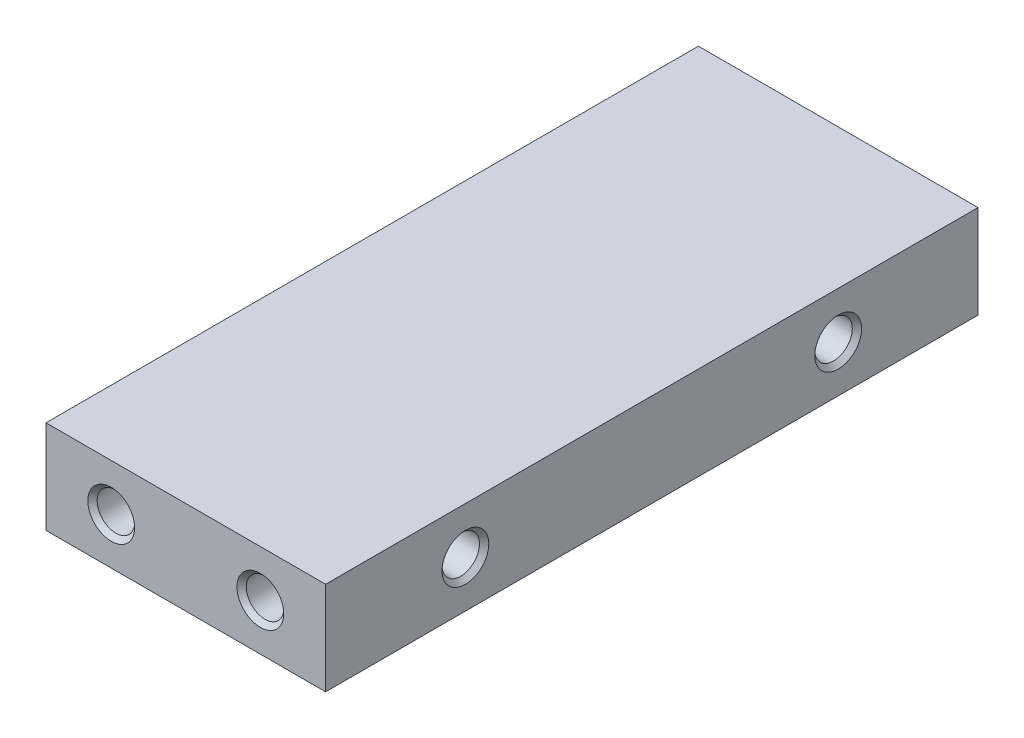
SolidWorks part; units mm, degrees
material "6063-T5"
ref_plane "Front Plane" through (0, 0, 0) normal (0, 0, 1) x (1, 0, 0)
ref_plane "Top Plane" through (0, 0, 0) normal (0, 1, 0) x (1, 0, 0)
ref_plane "Right Plane" through (0, 0, 0) normal (1, 0, 0) x (0, 0, -1)
sketch "Sketch1" plane through (0, 0, 0) normal (0, 0, 1) x (1, 0, 0)
  line L1 (-19.05, -6.35) -> (19.05, -6.35)
  line L2 (-19.05, -6.35) -> (-19.05, 6.35)
  line L3 (-19.05, 6.35) -> (19.05, 6.35)
  line L4 (19.05, -6.35) -> (19.05, 6.35)
  line L5 (-19.05, -6.35) -> (19.05, 6.35) construction
  line L6 (-19.05, 6.35) -> (19.05, -6.35) construction
  point P0 (0, 0)
  dimension "D1" = 38.1
  dimension "D2" = 12.7
extrude "Boss-Extrude1" add sketch "Sketch1" against normal blind 88.9
sketch "Sketch2" plane through (0, 0, 0) normal (0, 0, 1) x (1, 0, 0)
  line L1 (0, -1000) -> (0, 49000) construction
  point P0 (-10.16, 0)
  point P1 (10.16, 0)
  dimension "D1" = 20.32
hole_wizard "1/4-20 Tapped Hole1" positions "3DSketch1" profile "Sketch4" tap size "1/4-20" standard "ANSI Inch"
sketch3d "3DSketch1"
  point P0 (-10.16, 0, 0)
  point P3 (10.16, 0, 0)
sketch "Sketch4" plane through (-10.16, 0, 0) normal (1, 0, 0) x (0, -1, 0)
  line L0 (0, 0) -> (0, 15.5038)
  line L1 (0, 15.5038) -> (2.5527, 13.97)
  line L2 (2.5527, 13.97) -> (2.5527, 0.635)
  line L3 (2.5527, 0.635) -> (3.1877, 0)
  line L5 (3.1877, 0) -> (0, 0)
  line L6 (-2.5527, 0.635) -> (-3.1877, 0) construction
  line L10 (0, 15.5038) -> (-2.5527, 13.97) construction
  line L11 (0, -6.35) -> (0, 107.95) construction
  dimension "Tap Drill Dia." = 5.1054
  dimension "Tap Drill Depth" = 13.97
  dimension "Near C'Sink Dia." = 6.3754
  dimension "Near C'Sink Angle" = 90
  dimension "Drill Angle" = 118
cosmetic thread "Hole Thread1" parameters "D1"=12.7, "D2"=6.35
cosmetic thread "Hole Thread2" parameters "D1"=12.7, "D2"=6.35
ref_plane "Plane1" through (0, 0, -44.45) normal (0, 0, 1) x (1, 0, 0)
mirror "Mirror1" about plane through (0, 0, -44.45) normal (0, 0, 1) of "1/4-20 Tapped Hole1"
sketch "Sketch5" plane through (0, 6.35, 0) normal (0, 1, 0) x (1, 0, 0)
  line L0 (0, -1000) -> (0, 49000) construction
  line L1 (-999.1252, 44.45) -> (49000.8748, 44.45) construction
  line L3 (19.05, 0) -> (-19.05, 0) construction
  line L4 (19.05, 88.9) -> (-19.05, 88.9) construction
  point P4 (0, 82.55)
  point P6 (0, 6.35)
  dimension "D1" = 76.2
sketch "Sketch6" plane through (19.05, 0, 0) normal (1, 0, 0) x (0, 0, -1)
  line L0 (-953.1473, 0) -> (49046.8527, 0) construction
  line L1 (44.45, -1003.3371) -> (44.45, 48996.6629) construction
  line L3 (-201000, 6.35) -> (249000, 6.35) construction
  line L4 (88.9, -6.35) -> (0, -6.35) construction
  line L7 (44.45, 6.985) -> (44.45, -6.985) construction
  point P8 (69.85, 0)
  point P12 (19.05, 0)
  dimension "D1" = 50.8
hole_wizard "1/4-20 Tapped Hole2" positions "Sketch7" profile "Sketch8" tap size "1/4-20" standard "ANSI Inch"
sketch "Sketch7" plane through (19.05, 0, 0) normal (1, 0, 0) x (0, 0, -1)
  point P0 (19.05, 0)
  point P3 (69.85, 0)
sketch "Sketch8" plane through (19.05, 0, -19.05) normal (0, 1, 0) x (0, 0, -1)
  line L0 (0, 0) -> (0, 15.5038)
  line L1 (0, 15.5038) -> (2.5527, 13.97)
  line L2 (2.5527, 13.97) -> (2.5527, 0.635)
  line L3 (2.5527, 0.635) -> (3.1877, 0)
  line L5 (3.1877, 0) -> (0, 0)
  line L6 (-2.5527, 0.635) -> (-3.1877, 0) construction
  line L10 (0, 15.5038) -> (-2.5527, 13.97) construction
  line L11 (0, -6.35) -> (0, 107.95) construction
  dimension "Tap Drill Dia." = 5.1054
  dimension "Tap Drill Depth" = 13.97
  dimension "Near C'Sink Dia." = 6.3754
  dimension "Near C'Sink Angle" = 90
  dimension "Drill Angle" = 118
cosmetic thread "Hole Thread3" parameters "D1"=10.16, "D2"=6.35
cosmetic thread "Hole Thread4" parameters "D1"=10.16, "D2"=6.35
